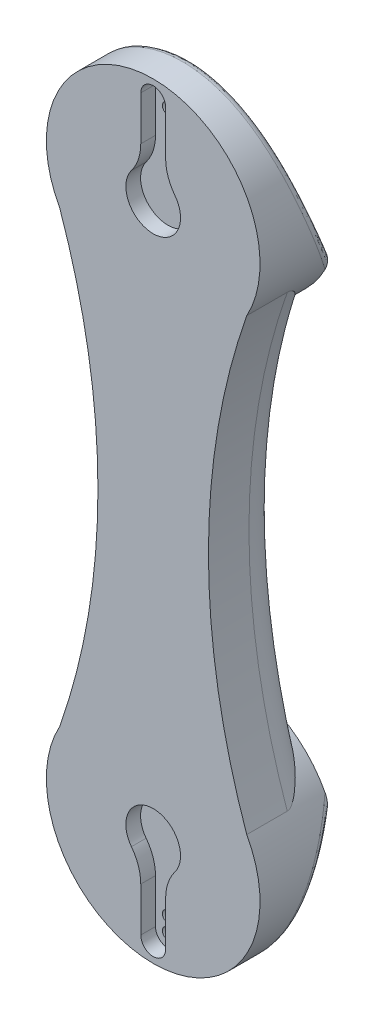
SolidWorks part; units mm, degrees
ref_plane "Front Plane" through (0, 0, 0) normal (0, 0, 1) x (1, 0, 0)
ref_plane "Top Plane" through (0, 0, 0) normal (0, 1, 0) x (1, 0, 0)
ref_plane "Right Plane" through (0, 0, 0) normal (1, 0, 0) x (0, 0, -1)
sketch "Sketch2" plane through (0, 0, 0) normal (0, 0, 1) x (1, 0, 0)
  line L0 (0, 150) -> (0, 0) construction
  circle A0 centre (0, 0) radius 29
  circle A1 centre (0, 150) radius 29
  arc A2 (-25.3969, 136) -> (-25.3969, 14) centre (-199.1469, 75) cw
  arc A3 (25.3969, 136) -> (25.3969, 14) centre (199.1469, 75) ccw
  point P5 (-15, 75)
  point P6 (0, 75)
  point P8 (15, 75)
  dimension "D1" = 58
  dimension "D2" = 150
  dimension "D3" = 15
  dimension "D4" = 14
  dimension "D5" = 14
extrude "Boss-Extrude1" add sketch "Sketch2" along normal blind 21 contours A1 | A1 L0 A0 A3 | L0 A1 A2 A0 | A0 region at (9.3139, 75, 0) region at (-9.3139, 75, 0) region at (-14.3307, 125.7363, 0) region at (14.3307, 24.2637, 0)
sketch "Sketch3" plane through (0, 0, 0) normal (1, 0, 0) x (0, 0, -1)
  line L0 (0, 179) -> (-11, 179)
  line L1 (0, 179) -> (-21, 179) construction
  line L2 (0, 14) -> (0, 136) construction
  line L3 (0, 179) -> (0, 141)
  line L4 (-21, 75) -> (0, 75) construction
  line L5 (-21, 136) -> (-21, 14) construction
  line L6 (0, -29) -> (0, 9)
  line L7 (0, -29) -> (-11, -29)
  arc A0 (-11, 179) -> (0, 141) centre (60.1364, 179) ccw
  arc A1 (-11, -29) -> (0, 9) centre (60.1364, -29) cw
  dimension "D1" = 11
  dimension "D2" = 38
extrude "Cut-Extrude1" cut sketch "Sketch3" against normal blind 30 and the other way blind 30
fillet "Fillet1" radius 10 2 edges at (-15, 75, 0) (15, 75, 0)
sketch "Sketch4" plane through (0, 0, 0) normal (0, 1, 0) x (1, 0, 0)
  circle A0 centre (0, -9) radius 5.75
  dimension "D1" = 11.5
  dimension "D2" = 9
extrude "Cut-Extrude2" cut sketch "Sketch4" along normal blind 105
fillet "Fillet2" radius 2 4 edges at (3.8746, 178.74, 10.9995) (-3.8746, -28.74, 10.9995) (0, 9, 0) (0, 141, 0)
sketch "Sketch5" plane through (0, 0, 21) normal (0, 0, 1) x (1, 0, 0)
  line L0 (-15, 75) -> (42.7958, 75) construction
  arc A0 (25.3969, 136) -> (-25.3969, 136) centre (0, 150) ccw construction
  arc A1 (25.3969, 136) -> (-25.3969, 136) centre (0, 150) ccw
  arc A2 (22.7696, 137.4483) -> (-22.7696, 137.4483) centre (0, 150) ccw
  circle A3 centre (0, 150) radius 26
  arc A4 (-25.3969, 14) -> (-25.3969, 136) centre (-199.1469, 75) ccw construction
  circle A5 centre (0, 0) radius 26
  arc A6 (22.7696, 12.5517) -> (-22.7696, 12.5517) centre (0, 0) cw
  arc A7 (25.3969, 14) -> (-25.3969, 14) centre (0, 0) cw
  dimension "D1" = 3
extrude "Cut-Extrude3" cut sketch "Sketch5" against normal blind 125 from offset 6 contours A2 A3 | A5 region at (0, 150, 21) region at (0, 0, 21) offset against normal yes
sketch "Sketch6" plane through (0, 0, 21) normal (0, 0, -1) x (-1, 0, 0)
  line L0 (0, 174) -> (0, 150) construction
  line L1 (-15.6865, 150) -> (15.6865, 150) construction
  line L2 (-15, 75) -> (15, 75) construction
  line L3 (-15.6865, 0) -> (15.6865, 0) construction
  line L4 (0, -24) -> (0, 0) construction
  line L5 (3.375, 174) -> (3.375, 162.0244)
  line L6 (-3.375, 174) -> (-3.375, 162.0244)
  line L9 (-3.375, -24) -> (-3.375, -12.0244)
  line L10 (3.375, -24) -> (3.375, -12.0244)
  arc A0 (-5.912, 154.4921) -> (5.912, 154.4921) centre (0, 150) ccw
  arc A1 (3.375, 174) -> (-3.375, 174) centre (0, 174) ccw
  arc A3 (-25.3969, 14) -> (-25.3969, 136) centre (-199.1469, 75) ccw construction
  arc A4 (25.3969, 136) -> (25.3969, 14) centre (199.1469, 75) ccw construction
  circle A10 centre (0, 174) radius 1.5
  circle A11 centre (0, 170) radius 1.5
  arc A16 (3.375, 162.0244) -> (5.912, 154.4921) centre (15.825, 162.0244) ccw
  arc A17 (-5.912, 154.4921) -> (-3.375, 162.0244) centre (-15.825, 162.0244) ccw
  circle A18 centre (0, -24) radius 1.5
  circle A19 centre (0, -20) radius 1.5
  arc A20 (-5.912, -4.4921) -> (-3.375, -12.0244) centre (-15.825, -12.0244) cw
  arc A21 (-5.912, -4.4921) -> (5.912, -4.4921) centre (0, 0) cw
  arc A22 (3.375, -12.0244) -> (5.912, -4.4921) centre (15.825, -12.0244) cw
  arc A23 (3.375, -24) -> (-3.375, -24) centre (0, -24) cw
  point P7 (0, 150)
  point P26 (0, 0)
  point P28 (0, 142.575)
  point P42 (0, 177.375)
  dimension "D1" = 14.85
  dimension "D2" = 6.75
  dimension "D4" = 12.45
  dimension "D5" = 4
  dimension "D6" = 3
  dimension "D7" = 3
  dimension "D12" = 12.45
  dimension "D3" = 34.8
extrude "Cut-Extrude4" cut sketch "Sketch6" along normal blind 50 contours A10 | A11 | A19 | A18
extrude "Cut-Extrude5" cut sketch "Sketch6<4>" along normal blind 4 contours L6 A17 A0 A16 L5 A1 | A20 L9 A23 L10 A22 A21
sketch "Sketch6<4>" plane through (0, 0, 21) normal (0, 0, -1) x (-1, 0, 0) same geometry as "Sketch6"
ref_plane "mid plane" through (0, 50, 0) normal (0, 1, 0) x (1, 0, 0)
